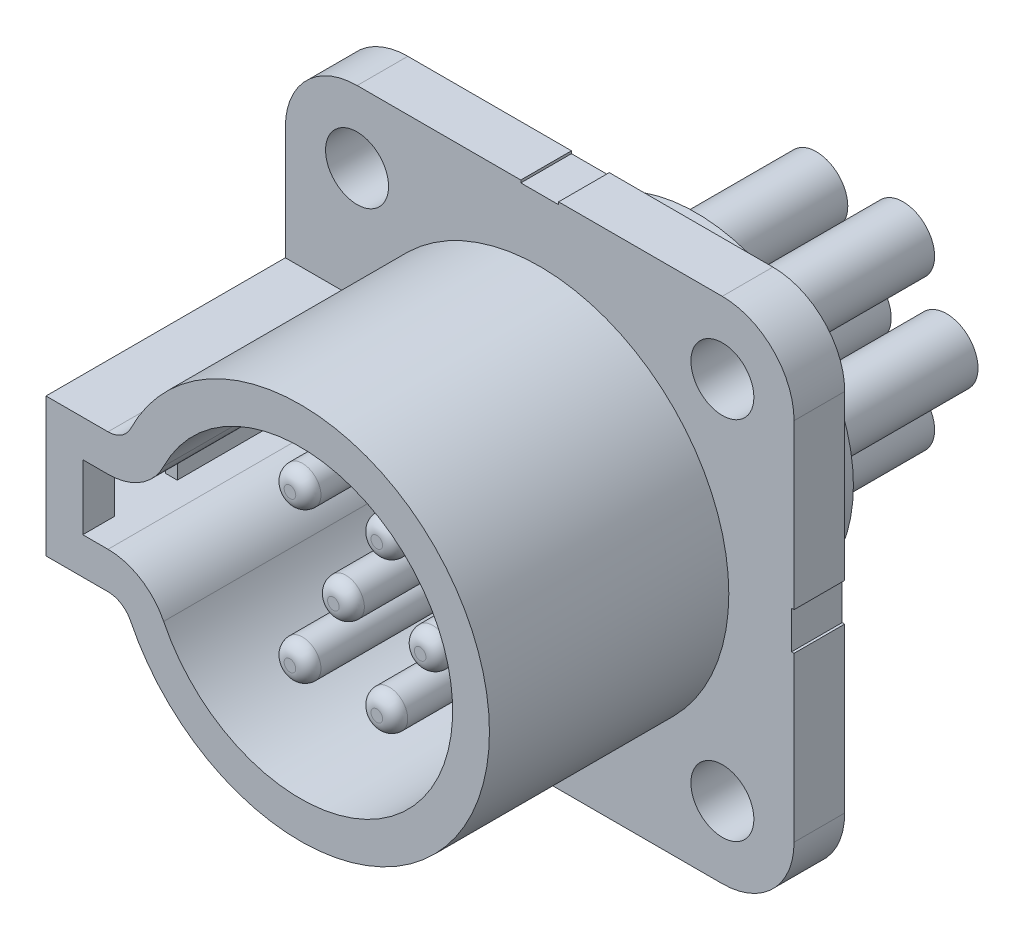
SolidWorks part; units mm, degrees
ref_plane "Front Plane" through (0, 0, 0) normal (0, 0, 1) x (1, 0, 0)
ref_plane "Top Plane" through (0, 0, 0) normal (0, 1, 0) x (1, 0, 0)
ref_plane "Right Plane" through (0, 0, 0) normal (1, 0, 0) x (0, 0, -1)
sketch "Sketch1" plane through (0, 0, 0) normal (0, 0, 1) x (1, 0, 0)
  line L1 (-10.095, 10.095) -> (10.095, 10.095)
  line L2 (-10.095, 10.095) -> (-10.095, -10.095)
  line L3 (-10.095, -10.095) -> (10.095, -10.095)
  line L4 (10.095, 10.095) -> (10.095, -10.095)
  line L5 (-10.095, 10.095) -> (10.095, -10.095) construction
  line L6 (-10.095, -10.095) -> (10.095, 10.095) construction
  point P0 (0, 0)
  dimension "D1" = 20.19
  dimension "D2" = 20.19
extrude "Boss-Extrude1" add sketch "Sketch1" along normal blind 2.01
sketch "Sketch2" plane through (0, 0, 2.01) normal (0, 0, 1) x (1, 0, 0)
  line L0 (0, 0) -> (0, 10.095) construction
  line L1 (10.095, 10.095) -> (-10.095, 10.095) construction
  line L2 (0, 0) -> (-10.095, 0) construction
  line L3 (-10.095, 10.095) -> (-10.095, -10.095) construction
  circle A0 centre (-7.25, 7.25) radius 1.25
  circle A1 centre (7.25, 7.25) radius 1.25
  circle A2 centre (7.25, -7.25) radius 1.25
  circle A3 centre (-7.25, -7.25) radius 1.25
  dimension "D1" = 2.5
  dimension "D2" = 7.25
  dimension "D3" = 7.25
extrude "Cut-Extrude1" cut sketch "Sketch2" against normal up to surface (2.01 mm away) up to face at (0, 0, 0)
fillet "Fillet1" radius 2.85 4 edges at (10.095, -10.095, 1.005) (-10.095, -10.095, 1.005) (10.095, 10.095, 1.005) (-10.095, 10.095, 1.005)
sketch "Sketch4" plane through (0, 0, 2.01) normal (0, 0, 1) x (1, 0, 0)
  line L0 (-10.095, -2.7495) -> (-10.095, 2.7495)
  line L1 (-10.095, 7.245) -> (-10.095, -7.245) construction
  line L2 (-10.095, 2.7495) -> (-7.6339, 2.7495)
  line L3 (-10.095, 0) -> (11.2357, 0) construction
  line L4 (-10.095, -2.7495) -> (-7.6339, -2.7495)
  line L5 (-8.635, -1.2895) -> (-8.635, 1.2895)
  line L6 (-8.635, 1.2895) -> (-7.6339, 1.2895)
  line L7 (-8.635, -1.2895) -> (-7.6339, -1.2895)
  line L8 (0, 10.095) -> (0, -11.6505) construction
  line L9 (7.245, 10.095) -> (-7.245, 10.095) construction
  line L10 (0, 6.045) -> (3.3385, 6.045) construction
  line L11 (0, -6.045) -> (3.3385, -6.045) construction
  line L12 (0, -7.505) -> (3.9298, -7.505) construction
  line L13 (0, 7.505) -> (4.2254, 7.505) construction
  arc A0 (-6.7363, 3.3086) -> (-6.7363, -3.3086) centre (0, 0) cw
  arc A1 (-6.7363, 3.3086) -> (-7.6339, 2.7495) centre (-7.6339, 3.7495) cw
  arc A2 (-6.7363, -3.3086) -> (-7.6339, -2.7495) centre (-7.6339, -3.7495) ccw
  arc A3 (-5.4259, 2.665) -> (-7.6339, 1.2895) centre (-7.6339, 3.7495) cw
  arc A4 (-5.4259, 2.665) -> (-5.4259, -2.665) centre (0, 0) cw
  arc A5 (-5.4259, -2.665) -> (-7.6339, -1.2895) centre (-7.6339, -3.7495) ccw
  dimension "D1" = 1
  dimension "D3" = 15.01
  dimension "D4" = 12.09
extrude "Boss-Extrude2" add sketch "Sketch4" along normal blind 9.5
sketch "Sketch5" plane through (-10.095, 0, 0) normal (-1, 0, 0) x (0, 0, 1)
  line L0 (0, 7.245) -> (0, -7.245) construction
  line L1 (0, 1.2895) -> (10.26, 1.2895)
  line L2 (0, 1.2895) -> (0, -1.2895)
  line L3 (0, -1.2895) -> (10.26, -1.2895)
  line L4 (10.26, 1.2895) -> (10.26, -1.2895)
  line L6 (0, 0) -> (-1.0293, 0) construction
  line L7 (11.51, 2.7495) -> (11.51, -2.7495) construction
  line L8 (11.51, 2.7495) -> (2.01, 2.7495) construction
  line L9 (11.51, -2.7495) -> (2.01, -2.7495) construction
  dimension "D1" = 1.25
  dimension "D2" = 1.46
  dimension "D3" = 1.46
extrude "Cut-Extrude2" cut sketch "Sketch5" against normal blind 1
sketch "Sketch6" plane through (-9.095, 0, 0) normal (-1, 0, 0) x (0, 0, 1)
  line L0 (0, -1.2895) -> (10.26, -1.2895) construction
  line L1 (10.26, 1.2895) -> (7.76, 1.2895)
  line L2 (10.26, 1.2895) -> (10.26, -1.2895)
  line L3 (10.26, -1.2895) -> (7.76, -1.2895)
  line L4 (7.76, 1.2895) -> (7.76, -1.2895)
  dimension "D1" = 2.5
extrude "Cut-Extrude3" cut sketch "Sketch6" against normal up to next
sketch "Sketch7" plane through (0, 0, 0) normal (0, 0, -1) x (-1, 0, 0)
  circle A0 centre (0, 0) radius 6.25
  dimension "D1" = 12.5
extrude "Boss-Extrude3" add sketch "Sketch7" along normal blind 4.19
sketch "Sketch8" plane through (0, 0, 2.01) normal (0, 0, 1) x (1, 0, 0)
  line L0 (-3.445, 0) -> (5.0962, 0) construction
  circle A0 centre (0, 0) radius 0.73
  circle A2 centre (3.445, 0) radius 0.73
  circle A3 centre (1.7225, 2.9835) radius 0.73
  circle A4 centre (-1.7225, 2.9835) radius 0.73
  circle A5 centre (1.7225, -2.9835) radius 0.73
  circle A6 centre (-1.7225, -2.9835) radius 0.73
  dimension "D1" = 1.46
extrude "Boss-Extrude4" add sketch "Sketch8" along normal blind 8.19 and the other way blind 7
fillet "Fillet2" radius 0.5 6 edges at (-2.4525, -2.9835, 10.2) (2.4525, 2.9835, 10.2) (0.9925, -2.9835, 10.2) (4.175, 0, 10.2) (0.73, 0, 10.2) (-0.9925, 2.9835, 10.2)
sketch "Sketch9" plane through (0, 0, -4.19) normal (0, 0, -1) x (-1, 0, 0)
  circle A0 centre (-1.7225, 2.9835) radius 1
  circle A1 centre (1.7225, 2.9835) radius 1
  circle A2 centre (0, 0) radius 1
  circle A3 centre (-3.445, 0) radius 1
  circle A4 centre (-1.7225, -2.9835) radius 1
  circle A5 centre (-1.7225, -2.9835) radius 1
  circle A6 centre (1.7225, -2.9835) radius 1
  point P0 (-1.7225, 2.9835)
  point P1 (1.7225, 2.9835)
  point P3 (-3.445, 0)
  point P5 (0, 0)
  point P7 (-1.7225, -2.9835)
  point P9 (1.7225, -2.9835)
  dimension "D1" = 2
  dimension "D2" = 2
  dimension "D3" = 2
  dimension "D4" = 2
  dimension "D5" = 2
  dimension "D6" = 2
extrude "Extrude-Thin1" add sketch "Sketch9" along normal blind 6.5 thin contours A0 | A1 | A2 | A3 | A4 | A6 thin type one direction wall 0.25
sketch "Sketch10" plane through (0, 10.095, 0) normal (0, 1, 0) x (1, 0, 0)
  line L0 (7.245, 0) -> (-7.245, 0) construction
  line L1 (-0.75, 0) -> (0.75, 0)
  line L2 (-0.75, 0) -> (-0.75, -2.01)
  line L3 (-0.75, -2.01) -> (0.75, -2.01)
  line L4 (0.75, 0) -> (0.75, -2.01)
  line L5 (7.245, -2.01) -> (-7.245, -2.01) construction
  line L6 (0, 4.99) -> (0, -4.274) construction
  line L7 (0.73, 4.99) -> (-0.73, 4.99) construction
  point P10 (0, -2.01)
  dimension "D1" = 1.5
  dimension "D2" = 0
extrude "Cut-Extrude4" cut sketch "Sketch10" against normal blind 0.1
sketch "Sketch12" plane through (10.095, 0, 0) normal (1, 0, 0) x (0, 0, -1)
  line L0 (-11.51, 0) -> (5.9037, 0)
  line L1 (-11.51, 7.505) -> (-11.51, -7.505) construction
  line L2 (0, -7.245) -> (0, 7.245) construction
  line L3 (-2.01, 0.75) -> (0, 0.75)
  line L4 (-2.01, 0.75) -> (-2.01, -0.75)
  line L5 (-2.01, -0.75) -> (0, -0.75)
  line L6 (0, 0.75) -> (0, -0.75)
  line L7 (-2.01, 0.75) -> (0, -0.75) construction
  line L8 (-2.01, -0.75) -> (0, 0.75) construction
  line L9 (-2.01, -7.245) -> (-2.01, 7.245) construction
  point P5 (-1.005, 0)
  point P12 (-2.01, 1.6013)
  dimension "D1" = 1.5
extrude "Cut-Extrude5" cut sketch "Sketch12" against normal blind 0.1 contours L3 L6 L5 L4
equation "\"D2@Sketch1\"=\"D1@Sketch1\""
equation "\"D3@Sketch5\"=\"D2@Sketch5\""
equation "\"D2@Sketch9\"=\"D1@Sketch9\""
equation "\"D3@Sketch9\"=\"D1@Sketch9\""
equation "\"D4@Sketch9\"=\"D1@Sketch9\""
equation "\"D5@Sketch9\"=\"D1@Sketch9\""
equation "\"D6@Sketch9\"=\"D1@Sketch9\""
